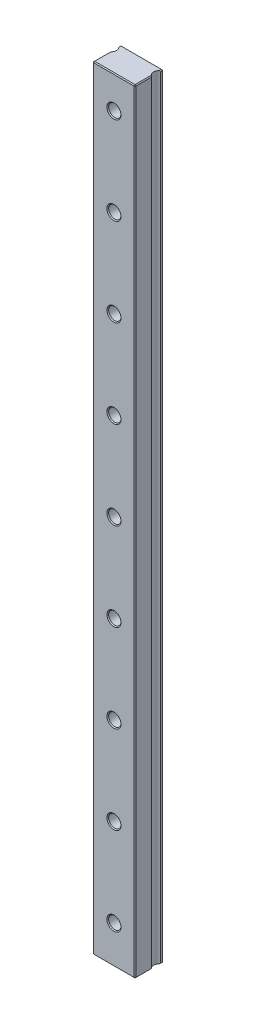
SolidWorks part; units mm, degrees
material "Chrome Stainless Steel"
ref_plane "Front" through (0, 0, 0) normal (0, 0, 1) x (1, 0, 0)
ref_plane "Top" through (0, 0, 0) normal (0, 1, 0) x (1, 0, 0)
ref_plane "Right" through (0, 0, 0) normal (1, 0, 0) x (0, 0, -1)
sketch "Sketch1" plane through (0, 0, 0) normal (0, 1, 0) x (1, 0, 0)
  line L0 (-6, 4) -> (-6, 2.75)
  line L1 (-6, 4) -> (6, 4)
  line L2 (-6, 4) -> (-6, -4)
  line L3 (-6, -4) -> (6, -4)
  line L4 (6, 4) -> (6, -4)
  line L5 (-6, 4) -> (6, -4) construction
  line L6 (-6, -4) -> (6, 4) construction
  line L7 (6, 4) -> (6, 2)
  line L8 (-6.75, 2) -> (6.75, 2) construction
  circle A0 centre (-6, 2) radius 0.75 construction
  circle A1 centre (6, 2) radius 0.75 construction
  arc A2 (-6, 0.701) -> (-6, 3.299) centre (-6.75, 2) ccw
  arc A3 (6, 3.299) -> (6, 0.701) centre (6.75, 2) ccw
  point P0 (0, 0)
  dimension "D1" = 8
  dimension "D2" = 12
extrude "Boss-Extrude1" add sketch "Sketch1" along normal blind 220 contours A3 L4 L1 L0 A2 L2 L3 region at (0, 0, 0.0593)
sketch "Sketch3" plane through (0, 0, -4) normal (0, 0, -1) x (-1, 0, 0)
  line L0 (6, 220) -> (6, 0) construction
  line L1 (-6, 0) -> (6, 0) construction
  line L2 (-6, 0) -> (-6, 10.75) construction
  line L3 (-6, 10.75) -> (6, 10.75) construction
  line L4 (6, 0) -> (6, 10.75) construction
  line L5 (-6, 0) -> (6, 10.75) construction
  line L6 (-6, 10.75) -> (6, 0) construction
  circle A0 centre (0, 10.75) radius 3.25
  circle A1 centre (0, 10.75) radius 1.75
  circle A2 centre (0, 35.75) radius 3.25
  circle A3 centre (0, 35.75) radius 1.75
  circle A4 centre (0, 60.75) radius 3.25
  circle A5 centre (0, 60.75) radius 1.75
  circle A6 centre (0, 85.75) radius 3.25
  circle A7 centre (0, 85.75) radius 1.75
  circle A8 centre (0, 110.75) radius 3.25
  circle A9 centre (0, 110.75) radius 1.75
  circle A10 centre (0, 135.75) radius 3.25
  circle A11 centre (0, 135.75) radius 1.75
  circle A12 centre (0, 160.75) radius 3.25
  circle A13 centre (0, 160.75) radius 1.75
  circle A14 centre (0, 185.75) radius 3.25
  circle A15 centre (0, 185.75) radius 1.75
  circle A16 centre (0, 210.75) radius 3.25
  circle A17 centre (0, 210.75) radius 1.75
  circle A18 centre (0, 235.75) radius 3.25
  circle A19 centre (0, 235.75) radius 1.75
  circle A20 centre (0, 260.75) radius 3.25
  circle A21 centre (0, 260.75) radius 1.75
  circle A22 centre (0, 285.75) radius 3.25
  circle A23 centre (0, 285.75) radius 1.75
  circle A24 centre (0, 310.75) radius 3.25
  circle A25 centre (0, 310.75) radius 1.75
  circle A26 centre (0, 335.75) radius 3.25
  circle A27 centre (0, 335.75) radius 1.75
  point P4 (0, 5.375)
  dimension "D1" = 14
extrude "Cut-Extrude3" cut sketch "Sketch3" against normal blind 8.5 contours A27 | A25 | A23 | A21 | A19 | A17 | A15 | A13 | A9 | A7 | A5 | A3 | A11 | A1 region at (0, 35.75, -4) region at (0, 60.75, -4) region at (0, 85.75, -4) region at (0, 110.75, -4) region at (0, 160.75, -4) region at (0, 185.75, -4) region at (0, 210.75, -4) region at (0, 235.75, -4) region at (0, 260.75, -4) region at (0, 285.75, -4) region at (0, 310.75, -4) region at (0, 335.75, -4)
extrude "Cut-Extrude4" cut sketch "Sketch3<6>" against normal blind 4.5
sketch "Sketch3<6>" plane through (0, 0, -4) normal (0, 0, -1) x (-1, 0, 0) same geometry as "Sketch3"
chamfer "Chamfer3" distance 0.25 angle 45 43 edges at (-1.75, 210.75, 4) (-1.75, 185.75, 4) (-1.75, 160.75, 4) (-1.75, 135.75, 4) (-1.75, 110.75, 4) (-1.75, 85.75, 4) (-1.75, 60.75, 4) (-1.75, 35.75, 4) (-1.75, 10.75, 4) (0, 0, 4) (6, 0, 1.6495) (-6, 0, 1.6495) (6, 220, 1.6495) (-6, 220, 1.6495) (6, 110, 4) (0, 220, 4) (-6, 110, 4) (6, 0, -3.6495) (-6, 0, -3.6495) (0, 0, -4) (6, 220, -3.6495) (-6, 220, -3.6495) (-6, 110, -4) (0, 220, -4) (6, 110, -4) (-3.25, 210.75, -4) (-1.75, 210.75, 0.5) (-3.25, 185.75, -4) (-1.75, 185.75, 0.5) (-3.25, 160.75, -4) (-1.75, 160.75, 0.5) (-3.25, 135.75, -4) (-1.75, 135.75, 0.5) (-3.25, 110.75, -4) (-1.75, 110.75, 0.5) (-3.25, 85.75, -4) (-1.75, 85.75, 0.5) (-3.25, 60.75, -4) (-1.75, 60.75, 0.5) (-3.25, 35.75, -4) (-1.75, 35.75, 0.5) (-3.25, 10.75, -4) (-1.75, 10.75, 0.5)
